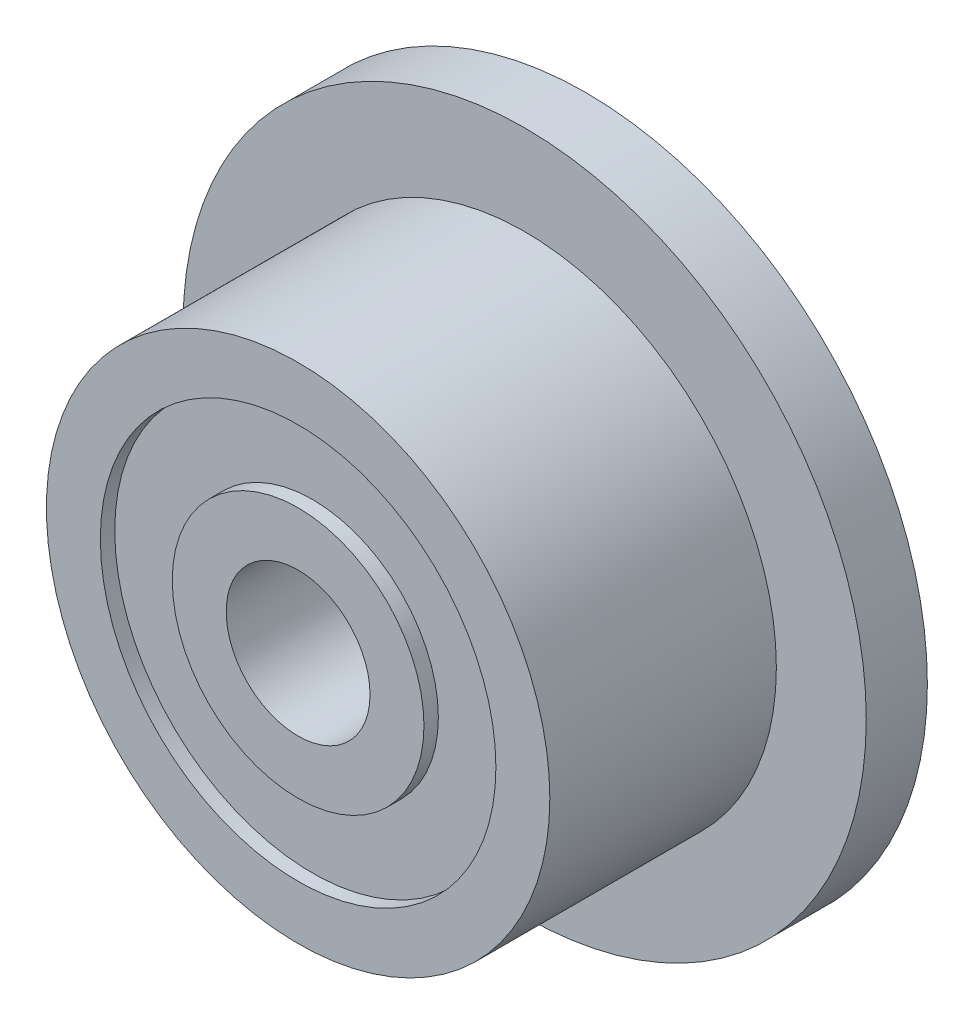
SolidWorks part; units mm, degrees
material "Stainless Steel (ferritic)"
ref_plane "Front Plane" through (0, 0, 0) normal (0, 0, 1) x (1, 0, 0)
ref_plane "Top Plane" through (0, 0, 0) normal (0, 1, 0) x (1, 0, 0)
ref_plane "Right Plane" through (0, 0, 0) normal (1, 0, 0) x (0, 0, -1)
sketch "Sketch1" plane through (0, 0, 0) normal (0, 0, 1) x (1, 0, 0)
  circle A1 centre (0, 0) radius 4.75
  dimension "D2" = 9.5
extrude "Boss-Extrude1" add sketch "Sketch1" along normal blind 0.85
sketch "Sketch3" plane through (0, 0, 0.85) normal (0, 0, 1) x (1, 0, 0)
  circle A0 centre (0, 0) radius 3.5
  dimension "D1" = 7
extrude "Boss-Extrude3" add sketch "Sketch3" along normal blind 3.15
sketch "Sketch4" plane through (0, 0, 4) normal (0, 0, 1) x (1, 0, 0)
  circle A0 centre (0, 0) radius 1
  dimension "D1" = 2
extrude "Cut-Extrude1" cut sketch "Sketch4" against normal blind 4
sketch "Sketch5" plane through (0, 0, 4) normal (0, 0, 1) x (1, 0, 0)
  circle A0 centre (0, 0) radius 1.75
  circle A1 centre (0, 0) radius 2.75
  dimension "D1" = 3.5
  dimension "D2" = 5.5
extrude "Cut-Extrude2" cut sketch "Sketch5" against normal blind 0.2
sketch "Sketch6" plane through (0, 0, 0) normal (0, 0, -1) x (-1, 0, 0)
  circle A0 centre (0, 0) radius 1.75
  circle A1 centre (0, 0) radius 2.75
  dimension "D1" = 5.5
  dimension "D2" = 3.5
extrude "Cut-Extrude3" cut sketch "Sketch6" against normal blind 0.2
ref_axis "Axis1" through (0, 0, 0) along (0, 0, 1)
equation "\"0.0.2cm\"=0.1"
